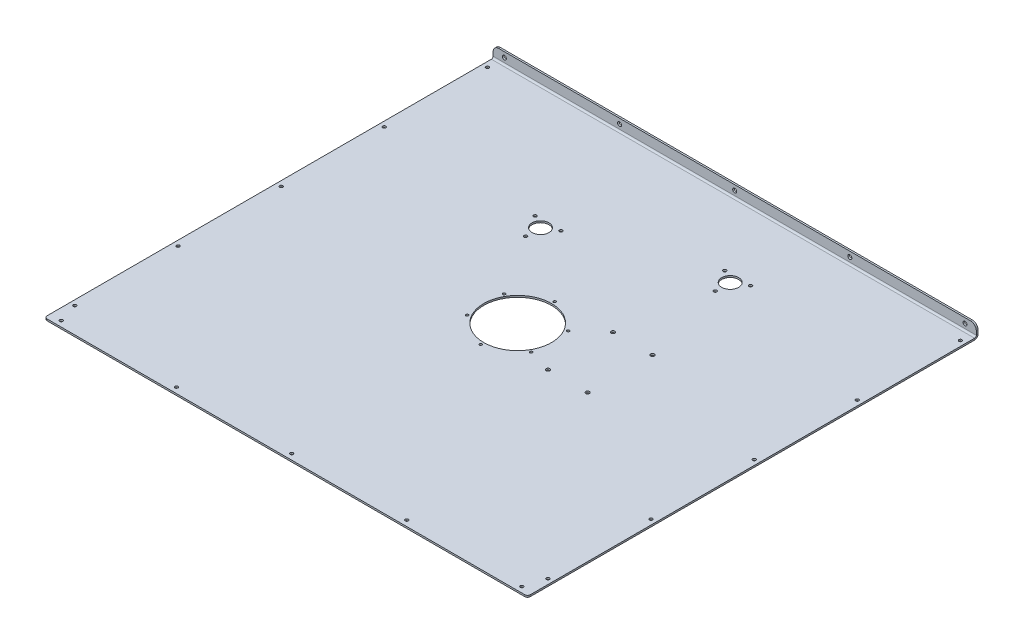
SolidWorks part; units mm, degrees
note: The reader was unsure of these and kept them because the rebuilt part matched: flange length of "Edge-Flange1".
material "AISI 304"
ref_plane "Front Plane" through (0, 0, 0) normal (0, 0, 1) x (1, 0, 0)
ref_plane "Top Plane" through (0, 0, 0) normal (0, 1, 0) x (1, 0, 0)
ref_plane "Right Plane" through (0, 0, 0) normal (1, 0, 0) x (0, 0, -1)
sketch "Sketch1" plane through (0, 0, 0) normal (0, 1, 0) x (1, 0, 0)
  line L0 (0, 387.5) -> (0, 0) construction
  line L1 (-428, -410.5) -> (428, -410.5)
  line L2 (-428, -410.5) -> (-428, 387.5)
  line L3 (-428, 387.5) -> (428, 387.5)
  line L4 (428, -410.5) -> (428, 387.5)
  point P0 (0, 0)
  dimension "D1" = 387.5
  dimension "D2" = 856
  dimension "D3" = 410.5
base flange "Base-Flange1" sketch "Sketch1" thickness 3 reverse thickness direction no parameters "D1"=3
sketch "Sketch8" plane through (0, 0, 0) normal (0, 1, 0) x (1, 0, 0)
  circle A0 centre (0, 0) radius 60
  dimension "D1" = 120
extrude "Cut-Extrude1" cut sketch "Sketch8" against normal blind 3 normal cut yes
hole_wizard "M4 Clearance Hole1" positions "Sketch9" profile "Sketch10" hole size "M4" standard "ISO" end condition through all
sketch "Sketch9" plane through (0, -3, 0) normal (0, -1, 0) x (-1, 0, 0)
  circle A1 centre (56.7247, 32.75) radius 1.65 construction
  point P0 (56.7247, 32.75)
sketch "Sketch10" plane through (-56.7247, -3, -32.75) normal (1, 0, 0) x (0, 0, -1)
  line L0 (0, 0) -> (0, 3)
  line L1 (0, 3) -> (2.25, 3)
  line L2 (2.25, 3) -> (2.25, 0)
  line L5 (2.25, 0) -> (0, 0)
  line L11 (0, -6.35) -> (0, 107.95) construction
  dimension "Thru Hole Dia." = 4.5
  dimension "Thru Hole Depth" = 3
pattern_circular "CirPattern1" count 6 over 360 about axis through (0, 0, 0) along (0, 1, 0) of "M4 Clearance Hole1"
edge flange "Edge-Flange1" sketch "Sketch15" flange angle 90 flange length 20 flange position material inside bend radius 3 thickness 3 relief rectangular parameters "D1"=2, "D6"=10
sketch "Sketch15" plane through (0, 0, -387.5) normal (0, 0, -1) x (-1, 0, 0)
  line L2 (-428, 0) -> (-428, 20)
  line L3 (-428, 20) -> (428, 20)
  line L4 (428, 20) -> (428, 0)
  line L7 (-428, 0) -> (428, 0) construction
  line L8 (-428, 0) -> (428, 0)
bend "EdgeBend1" bend radius 3 bend angle 90 parameters "D5"=1
hole_wizard "M5 Clearance Hole3" positions "Sketch20" profile "Sketch21" hole size "M5" standard "ISO" end condition through all
sketch "Sketch20" plane through (0, -3, 0) normal (0, -1, 0) x (-1, 0, 0)
  point P0 (419, 365.4)
  point P4 (419, 182.7)
  point P7 (419, 0)
  point P10 (419, -182.7)
  point P13 (419, -365.4)
sketch "Sketch21" plane through (-419, -3, -365.4) normal (1, 0, 0) x (0, 0, -1)
  line L0 (0, 0) -> (0, 23)
  line L1 (0, 23) -> (2.75, 23)
  line L2 (2.75, 23) -> (2.75, 0)
  line L5 (2.75, 0) -> (0, 0)
  line L11 (0, -6.35) -> (0, 107.95) construction
  dimension "Thru Hole Dia." = 5.5
  dimension "Thru Hole Depth" = 23
mirror "Mirror2" about plane through (0, 0, 0) normal (1, 0, 0) of "M5 Clearance Hole3"
hole_wizard "M5 Clearance Hole4" positions "Sketch22" profile "Sketch23" hole size "M5" standard "ISO" end condition through all
sketch "Sketch22" plane through (0, 0, 0) normal (0, 1, 0) x (1, 0, 0)
  line L0 (-428, -410.5) -> (428, -410.5) construction
  line L1 (-428, 381.5) -> (-428, -410.5) construction
  point P0 (-408, -400.5)
  dimension "D1" = 10
  dimension "D2" = 20
sketch "Sketch23" plane through (-408, 0, 400.5) normal (1, 0, 0) x (0, 0, 1)
  line L0 (0, 0) -> (0, 3)
  line L1 (0, 3) -> (2.75, 3)
  line L2 (2.75, 3) -> (2.75, 0)
  line L5 (2.75, 0) -> (0, 0)
  line L11 (0, -6.35) -> (0, 107.95) construction
  dimension "Thru Hole Dia." = 5.5
  dimension "Thru Hole Depth" = 3
pattern_linear "LPattern1" count 5 spacing 204 along (1, 0, 0) of "M5 Clearance Hole4"
hole_wizard "Ø7.1 (7.1) Diameter Hole1" positions "Sketch24" profile "Sketch25" hole size "Ø7.1" standard "ISO" end condition through all
sketch "Sketch24" plane through (0, 0, -384.5) normal (0, 0, 1) x (1, 0, 0)
  line L0 (-428, 3) -> (-428, 20) construction
  line L1 (-428, 20) -> (428, 20) construction
  point P0 (-408, 11)
  dimension "D1" = 20
  dimension "D2" = 9
sketch "Sketch25" plane through (-408, 11, -384.5) normal (1, 0, 0) x (0, -1, 0)
  line L0 (0, 0) -> (0, 3)
  line L1 (0, 3) -> (3.55, 3)
  line L2 (3.55, 3) -> (3.55, 0)
  line L5 (3.55, 0) -> (0, 0)
  line L11 (0, -6.35) -> (0, 107.95) construction
  dimension "Thru Hole Dia." = 7.1
  dimension "Thru Hole Depth" = 3
pattern_linear "LPattern2" count 5 spacing 204 along (1, 0, 0) of "Ø7.1 (7.1) Diameter Hole1"
sketch "Sketch26" plane through (0, -3, 0) normal (0, -1, 0) x (-1, 0, 0)
  circle A0 centre (126.0075, 166.5008) radius 15
  circle A1 centre (126.0075, 166.5008) radius 20 construction
  dimension "D2" = 30
extrude "Cut-Extrude2" cut sketch "Sketch26" against normal blind 3 normal cut yes
hole_wizard "M5 Clearance Hole6" positions "Sketch27" profile "Sketch28" hole size "M5" standard "ISO" end condition through all
sketch "Sketch27" plane through (0, -3, 0) normal (0, -1, 0) x (-1, 0, 0)
  point P0 (148.8706, 179.7008)
  point P2 (126.0075, 140.1008)
  point P5 (103.1444, 179.7008)
sketch "Sketch28" plane through (-148.8706, -3, -179.7008) normal (1, 0, 0) x (0, 0, -1)
  line L0 (0, 0) -> (0, 23)
  line L1 (0, 23) -> (2.75, 23)
  line L2 (2.75, 23) -> (2.75, 0)
  line L5 (2.75, 0) -> (0, 0)
  line L11 (0, -6.35) -> (0, 107.95) construction
  dimension "Thru Hole Dia." = 5.5
  dimension "Thru Hole Depth" = 23
fillet "Fillet1" radius 5 2 edges at (428, -1.5, 410.5) (-428, -1.5, 410.5)
fillet "Fillet2" radius 10 2 edges at (428, 20, -386) (-428, 20, -386)
sketch "Sketch29" plane through (0, 0, 0) normal (0, 1, 0) x (1, 0, 0)
  circle A0 centre (126, 250.5008) radius 15
  circle A1 centre (-126.0075, 166.5008) radius 15 construction
  circle A2 centre (126, 250.5008) radius 17.5 construction
extrude "Cut-Extrude3" cut sketch "Sketch29" against normal blind 10
hole_wizard "M5 Clearance Hole7" positions "Sketch30" profile "Sketch31" hole size "M5" standard "ISO" end condition through all
sketch "Sketch30" plane through (0, 0, 0) normal (0, 1, 0) x (1, 0, 0)
  line L0 (126, 224.0008) -> (126, 250.5008) construction
  point P0 (126, 224.0008)
  dimension "D1" = 26.5
sketch "Sketch31" plane through (126, 0, -224.0008) normal (1, 0, 0) x (0, 0, 1)
  line L0 (0, 0) -> (0, 3)
  line L1 (0, 3) -> (2.75, 3)
  line L2 (2.75, 3) -> (2.75, 0)
  line L5 (2.75, 0) -> (0, 0)
  line L11 (0, -6.35) -> (0, 107.95) construction
  dimension "Thru Hole Dia." = 5.5
  dimension "Thru Hole Depth" = 3
pattern_circular "CirPattern2" count 3 over 360 about axis through (126, 0, -250.5008) along (0, 1, 0) of "M5 Clearance Hole7" reverse direction yes
hole_wizard "M6 Clearance Hole1" positions "Sketch32" profile "Sketch33" hole size "M6" standard "ISO" end condition through all
sketch "Sketch32" plane through (0, 0, 0) normal (0, 1, 0) x (1, 0, 0)
  point P0 (98.5, -44.65)
  point P3 (168.5, -44.65)
  point P6 (168.5, 70.35)
  point P9 (98.5, 70.35)
sketch "Sketch33" plane through (98.5, 0, 44.65) normal (1, 0, 0) x (0, 0, 1)
  line L0 (0, 0) -> (0, 3)
  line L1 (0, 3) -> (3.3, 3)
  line L2 (3.3, 3) -> (3.3, 0)
  line L5 (3.3, 0) -> (0, 0)
  line L11 (0, -6.35) -> (0, 107.95) construction
  dimension "Thru Hole Dia." = 6.6
  dimension "Thru Hole Depth" = 3
sketch "Bend-Lines1" [suppressed] plane through (0, 0, 0) normal (0, 1, 0) x (1, 0, 0)
sketch "Bounding-Box1" [suppressed] plane through (0, 0, 0) normal (0, 1, 0) x (1, 0, 0)
sheet metal parameters "Sheet-Metal1" thickness 3 parameters "D1"=1
flat pattern "Flat-Pattern1" [suppressed]
sketch "Bend-Lines2" plane through (0, 0, 0) normal (0, 1, 0) x (1, 0, 0)
sketch3d "Bounding-Box2" [suppressed]
  line L0 (448, 350, 0) -> (-448, 350, 0) construction
  line L1 (448, -350, 0) -> (-448, -350, 0) construction
  line L2 (448, 350, 0) -> (448, -350, 0) construction
  line L3 (-448, 350, 0) -> (-448, -350, 0) construction
sheet metal parameters "Sheet-Metal3" thickness 3 parameters "D1"=1
flat pattern "Flat-Pattern1"
sketch "Bend-Lines2" plane through (0, 0, 0) normal (0, 1, 0) x (1, 0, 0)
  line L0 (346.3034, -350) -> (346.3034, 345.1945) construction
  line L1 (345.1945, 346.3034) -> (-345.1945, 346.3034) construction
  line L2 (-346.3034, 345.1945) -> (-346.3034, -350) construction
  line L3 (346.3034, -350) -> (346.3034, 345.1945) construction
  line L4 (345.1945, 346.3034) -> (-345.1945, 346.3034) construction
  line L5 (-346.3034, 345.1945) -> (-346.3034, -350) construction
sketch3d "Bounding-Box2" [suppressed]
  line L0 (-369.8494, -380, 0) -> (-369.8494, 369.8494, 0) construction
  line L1 (369.8494, -380, 0) -> (369.8494, 369.8494, 0) construction
  line L2 (-369.8494, -380, 0) -> (369.8494, -380, 0) construction
  line L3 (-369.8494, 369.8494, 0) -> (369.8494, 369.8494, 0) construction
sheet metal parameters "Sheet-Metal4" thickness 3 parameters "D1"=1
flat pattern "Flat-Pattern1"
sketch "Bend-Lines2" plane through (0, 0, 0) normal (0, 1, 0) x (1, 0, 0)
  line L0 (421.3034, -350) -> (421.3034, 345.1945) construction
  line L1 (420.1945, 346.3034) -> (-420.1945, 346.3034) construction
  line L2 (-421.3034, 345.1945) -> (-421.3034, -350) construction
  line L3 (421.3034, -350) -> (421.3034, 345.1945) construction
  line L4 (420.1945, 346.3034) -> (-420.1945, 346.3034) construction
  line L5 (-421.3034, 345.1945) -> (-421.3034, -350) construction
sketch3d "Bounding-Box2" [suppressed]
  line L0 (444.8494, 369.8494, 0) -> (-444.8494, 369.8494, 0) construction
  line L1 (444.8494, -380, 0) -> (-444.8494, -380, 0) construction
  line L2 (444.8494, 369.8494, 0) -> (444.8494, -380, 0) construction
  line L3 (-444.8494, 369.8494, 0) -> (-444.8494, -380, 0) construction
sheet metal parameters "Sheet-Metal5" thickness 3 parameters "D1"=1
flat pattern "Flat-Pattern1"
sketch "Bend-Lines2" plane through (0, 0, 0) normal (0, 1, 0) x (1, 0, 0)
  point P0 (421.3034, -350)
  point P1 (421.3034, 345.1945)
  point P2 (420.1945, 346.3034)
  point P3 (-420.1945, 346.3034)
  point P4 (-421.3034, 345.1945)
  point P5 (-421.3034, -350)
sketch3d "Bounding-Box2" [suppressed]
  line L0 (448, 350, 0) -> (-448, 350, 0) construction
  line L1 (448, -350, 0) -> (-448, -350, 0) construction
  line L2 (448, 350, 0) -> (448, -350, 0) construction
  line L3 (-448, 350, 0) -> (-448, -350, 0) construction
sheet metal parameters "Sheet-Metal7" thickness 3 parameters "D1"=1
flat pattern "Flat-Pattern1"
sketch "Bend-Lines2" plane through (0, 0, 0) normal (0, 1, 0) x (1, 0, 0)
  line L0 (448, 372.7489) -> (-448, 372.7489) construction
  line L1 (448, 372.7489) -> (-448, 372.7489) construction
sketch3d "Bounding-Box2" [suppressed]
  line L0 (448, 393.4978, 0) -> (-448, 393.4978, 0) construction
  line L1 (448, -405, 0) -> (-448, -405, 0) construction
  line L2 (448, 393.4978, 0) -> (448, -405, 0) construction
  line L3 (-448, 393.4978, 0) -> (-448, -405, 0) construction
bend of the flat pattern "Flatten-<EdgeBend1>1"
sheet metal parameters "Sheet-Metal11" thickness 3 parameters "D1"=1
flat pattern "Flat-Pattern1"
sketch "Bend-Lines2" plane through (0, 0, 0) normal (0, 1, 0) x (1, 0, 0)
  line L0 (448, 372.7489) -> (-448, 372.7489) construction
  line L1 (448, 372.7489) -> (-448, 372.7489) construction
sketch3d "Bounding-Box2" [suppressed]
  line L0 (448, 393.4978, 0) -> (-448, 393.4978, 0) construction
  line L1 (448, -405, 0) -> (-448, -405, 0) construction
  line L2 (448, 393.4978, 0) -> (448, -405, 0) construction
  line L3 (-448, 393.4978, 0) -> (-448, -405, 0) construction
bend of the flat pattern "Flatten-<EdgeBend1>1"
sheet metal parameters "Sheet-Metal12" thickness 3 parameters "D1"=1
flat pattern "Flat-Pattern1"
sketch "Bend-Lines2" plane through (0, 0, 0) normal (0, 1, 0) x (1, 0, 0)
  line L0 (448, 372.7489) -> (-448, 372.7489) construction
  line L1 (448, 372.7489) -> (-448, 372.7489) construction
sketch3d "Bounding-Box2" [suppressed]
  line L0 (448, 393.4978, 0) -> (-448, 393.4978, 0) construction
  line L1 (448, -405, 0) -> (-448, -405, 0) construction
  line L2 (448, 393.4978, 0) -> (448, -405, 0) construction
  line L3 (-448, 393.4978, 0) -> (-448, -405, 0) construction
bend of the flat pattern "Flatten-<EdgeBend1>1"
sheet metal parameters "Sheet-Metal13" thickness 3 parameters "D1"=1
flat pattern "Flat-Pattern1"
sketch "Bend-Lines2" plane through (0, 0, 0) normal (0, 1, 0) x (1, 0, 0)
  line L0 (448, 372.7489) -> (-448, 372.7489) construction
  line L1 (448, 372.7489) -> (-448, 372.7489) construction
sketch3d "Bounding-Box2" [suppressed]
  line L0 (448, 393.4978, 0) -> (-448, 393.4978, 0) construction
  line L1 (448, -405, 0) -> (-448, -405, 0) construction
  line L2 (448, 393.4978, 0) -> (448, -405, 0) construction
  line L3 (-448, 393.4978, 0) -> (-448, -405, 0) construction
bend of the flat pattern "Flatten-<EdgeBend1>1"
sheet metal parameters "Sheet-Metal14" thickness 3 parameters "D1"=1
flat pattern "Flat-Pattern1"
sketch "Bend-Lines2" plane through (0, 0, 0) normal (0, 1, 0) x (1, 0, 0)
  line L0 (448, 372.7489) -> (-448, 372.7489) construction
  line L1 (448, 372.7489) -> (-448, 372.7489) construction
sketch3d "Bounding-Box2" [suppressed]
  line L0 (448, 393.4978, 0) -> (-448, 393.4978, 0) construction
  line L1 (448, -405, 0) -> (-448, -405, 0) construction
  line L2 (448, 393.4978, 0) -> (448, -405, 0) construction
  line L3 (-448, 393.4978, 0) -> (-448, -405, 0) construction
bend of the flat pattern "Flatten-<EdgeBend1>1"
sheet metal parameters "Sheet-Metal15" thickness 3 parameters "D1"=1
flat pattern "Flat-Pattern1"
sketch "Bend-Lines2" plane through (0, 0, 0) normal (0, 1, 0) x (1, 0, 0)
  line L0 (448, 372.7489) -> (-448, 372.7489) construction
  line L1 (448, 372.7489) -> (-448, 372.7489) construction
sketch3d "Bounding-Box2" [suppressed]
  line L0 (448, 393.4978, 0) -> (-448, 393.4978, 0) construction
  line L1 (448, -405, 0) -> (-448, -405, 0) construction
  line L2 (448, 393.4978, 0) -> (448, -405, 0) construction
  line L3 (-448, 393.4978, 0) -> (-448, -405, 0) construction
bend of the flat pattern "Flatten-<EdgeBend1>1"
sheet metal parameters "Sheet-Metal16" thickness 3 parameters "D1"=1
flat pattern "Flat-Pattern1"
sketch "Bend-Lines2" plane through (0, 0, 0) normal (0, 1, 0) x (1, 0, 0)
  line L0 (428, 385.2489) -> (-428, 385.2489) construction
  line L1 (428, 385.2489) -> (-428, 385.2489) construction
sketch3d "Bounding-Box2" [suppressed]
  line L0 (428, 405.9978, 0) -> (-428, 405.9978, 0) construction
  line L1 (428, -405, 0) -> (-428, -405, 0) construction
  line L2 (428, 405.9978, 0) -> (428, -405, 0) construction
  line L3 (-428, 405.9978, 0) -> (-428, -405, 0) construction
bend of the flat pattern "Flatten-<EdgeBend1>1"
sheet metal parameters "Sheet-Metal17" thickness 3 parameters "D1"=1
flat pattern "Flat-Pattern1"
sketch "Bend-Lines2" plane through (0, 0, 0) normal (0, 1, 0) x (-1, 0, 0)
  line L0 (-428, -385.2489) -> (428, -385.2489) construction
  line L1 (-428, -385.2489) -> (428, -385.2489) construction
sketch3d "Bounding-Box2" [suppressed]
  line L0 (-428, -405.9978, 0) -> (428, -405.9978, 0) construction
  line L1 (-428, 405, 0) -> (428, 405, 0) construction
  line L2 (-428, -405.9978, 0) -> (-428, 405, 0) construction
  line L3 (428, -405.9978, 0) -> (428, 405, 0) construction
bend of the flat pattern "Flatten-<EdgeBend1>1"
sheet metal parameters "Sheet-Metal18" thickness 3 parameters "D1"=1
flat pattern "Flat-Pattern1"
sketch "Bend-Lines2" plane through (0, 0, 0) normal (0, 1, 0) x (1, 0, 0)
  line L0 (428, 385.2489) -> (-428, 385.2489) construction
  line L1 (428, 385.2489) -> (-428, 385.2489) construction
sketch3d "Bounding-Box2" [suppressed]
  line L0 (-428, 405.9977, 0) -> (428, 405.9978, 0) construction
  line L1 (-427.9999, -412.5, 0) -> (428.0001, -412.4999, 0) construction
  line L2 (-428, 405.9977, 0) -> (-427.9999, -412.5, 0) construction
  line L3 (428, 405.9978, 0) -> (428.0001, -412.4999, 0) construction
bend of the flat pattern "Flatten-<EdgeBend1>1"
sheet metal parameters "Sheet-Metal19" thickness 3 parameters "D1"=1
flat pattern "Flat-Pattern1"
sketch "Bend-Lines2" plane through (0, 0, 0) normal (0, 1, 0) x (1, 0, 0)
  line L0 (428, 385.2489) -> (-428, 385.2489) construction
  line L1 (428, 385.2489) -> (-428, 385.2489) construction
sketch3d "Bounding-Box2" [suppressed]
  line L0 (-428, 405.9977, 0) -> (428, 405.9978, 0) construction
  line L1 (-427.9999, -412.5, 0) -> (428.0001, -412.4999, 0) construction
  line L2 (-428, 405.9977, 0) -> (-427.9999, -412.5, 0) construction
  line L3 (428, 405.9978, 0) -> (428.0001, -412.4999, 0) construction
bend of the flat pattern "Flatten-<EdgeBend1>1"
sheet metal parameters "Sheet-Metal20" thickness 3 parameters "D1"=1
flat pattern "Flat-Pattern1"
sketch "Bend-Lines2" plane through (0, 0, 0) normal (0, 1, 0) x (1, 0, 0)
  line L0 (428, 385.2489) -> (-428, 385.2489) construction
  line L1 (428, 385.2489) -> (-428, 385.2489) construction
sketch3d "Bounding-Box2" [suppressed]
  line L0 (-428, 405.9977, 0) -> (428, 405.9978, 0) construction
  line L1 (-427.9999, -412.5, 0) -> (428.0001, -412.4999, 0) construction
  line L2 (-428, 405.9977, 0) -> (-427.9999, -412.5, 0) construction
  line L3 (428, 405.9978, 0) -> (428.0001, -412.4999, 0) construction
bend of the flat pattern "Flatten-<EdgeBend1>1"
sheet metal parameters "Sheet-Metal21" thickness 3 parameters "D1"=1
flat pattern "Flat-Pattern1"
sketch "Bend-Lines2" plane through (0, 0, 0) normal (0, 1, 0) x (1, 0, 0)
  line L0 (428, 385.2489) -> (-428, 385.2489) construction
  line L1 (428, 385.2489) -> (-428, 385.2489) construction
sketch3d "Bounding-Box2" [suppressed]
  line L0 (-428, 405.9977, 0) -> (428, 405.9978, 0) construction
  line L1 (-427.9999, -412.5, 0) -> (428.0001, -412.4999, 0) construction
  line L2 (-428, 405.9977, 0) -> (-427.9999, -412.5, 0) construction
  line L3 (428, 405.9978, 0) -> (428.0001, -412.4999, 0) construction
bend of the flat pattern "Flatten-<EdgeBend1>1"
sheet metal parameters "Sheet-Metal22" thickness 3 parameters "D1"=1
flat pattern "Flat-Pattern1"
sketch "Bend-Lines2" plane through (0, 0, 0) normal (0, 1, 0) x (1, 0, 0)
  line L0 (428, 385.0343) -> (-428, 385.0343) construction
  line L1 (428, 385.0343) -> (-428, 385.0343) construction
sketch3d "Bounding-Box2" [suppressed]
  line L0 (-428, 405.5685, 0) -> (428, 405.5686, 0) construction
  line L1 (-427.9999, -410.5, 0) -> (428.0001, -410.4999, 0) construction
  line L2 (-428, 405.5685, 0) -> (-427.9999, -410.5, 0) construction
  line L3 (428, 405.5686, 0) -> (428.0001, -410.4999, 0) construction
bend of the flat pattern "Flatten-<EdgeBend1>1"
